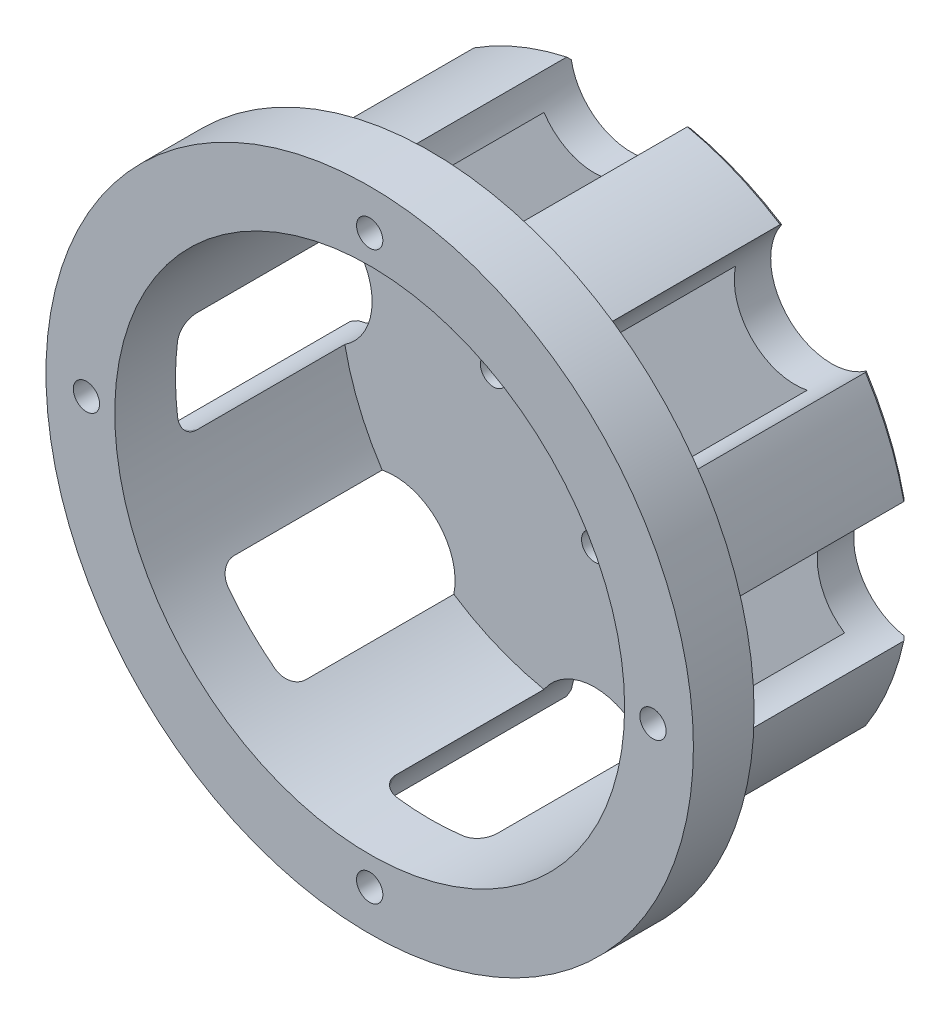
SolidWorks part; units mm, degrees
material "ABS PC"
ref_plane "Front Plane" through (0, 0, 0) normal (0, 0, 1) x (1, 0, 0)
ref_plane "Top Plane" through (0, 0, 0) normal (0, 1, 0) x (1, 0, 0)
ref_plane "Right Plane" through (0, 0, 0) normal (1, 0, 0) x (0, 0, -1)
sketch "Sketch1" plane through (0, 0, 0) normal (0, 0, 1) x (1, 0, 0)
  circle A0 centre (0, 0) radius 31.5
  circle A1 centre (0, 0) radius 35
  circle A2 centre (0, 0) radius 7
  circle A3 centre (0, 0) radius 12.5
  circle A4 centre (0, 12.5) radius 1.625
  circle A5 centre (12.5, 0) radius 1.625
  circle A6 centre (0, -12.5) radius 1.625
  circle A7 centre (-12.5, 0) radius 1.625
  point P17 (0, 0)
  dimension "D1" = 63
  dimension "D2" = 70
  dimension "D3" = 14
  dimension "D4" = 25
  dimension "D5" = 3.25
  dimension "D6" = 4
extrude "Boss-Extrude1" add sketch "Sketch1" along normal blind 4.5 contours A0 A7 A3 A4 A5 A6 | A7 A3 A6 A5 A4 A2 region at (-30.609, 0, 0) region at (10.5244, 0, 0)
extrude "Boss-Extrude2" add sketch "Sketch1<3>" along normal blind 32.3 contours A1 A0 region at (-34.0101, 0, 0)
sketch "Sketch1<3>" plane through (0, 0, 0) normal (0, 0, 1) x (1, 0, 0) same geometry as "Sketch1"
sketch "Sketch2" plane through (0, 0, 0) normal (0, 0, -1) x (-1, 0, 0)
  circle A0 centre (0, 35) radius 7.5
  circle A1 centre (0, 0) radius 35 construction
  circle A2 centre (24.7487, 24.7487) radius 7.5
  circle A3 centre (35, 0) radius 7.5
  circle A4 centre (24.7487, -24.7487) radius 7.5
  circle A5 centre (0, -35) radius 7.5
  circle A6 centre (-24.7487, -24.7487) radius 7.5
  circle A7 centre (-35, 0) radius 7.5
  circle A8 centre (-24.7487, 24.7487) radius 7.5
  point P20 (0, 0)
  dimension "D1" = 15
  dimension "D2" = 8
extrude "Cut-Extrude1" cut sketch "Sketch2" against normal blind 27.5
sketch "Sketch3" plane through (0, 0, 32.3) normal (0, 0, 1) x (1, 0, 0)
  circle A0 centre (0, 0) radius 40
  circle A1 centre (0, 0) radius 31.5
  dimension "D1" = 80
  dimension "D2" = 63
extrude "Boss-Extrude3" add sketch "Sketch3" against normal blind 7.5
sketch "Sketch4" plane through (0, 0, 32.3) normal (0, 0, 1) x (1, 0, 0)
  circle A0 centre (0, 35) radius 1.625
  circle A1 centre (35, 0) radius 1.625
  circle A2 centre (0, -35) radius 1.625
  circle A3 centre (-35, 0) radius 1.625
  point P13 (0, 0)
  dimension "D1" = 3.25
  dimension "D2" = 4
extrude "Cut-Extrude2" cut sketch "Sketch4" against normal blind 10
fillet "Fillet1" radius 2 24 edges at (-32.4625, -7.0577, 24.8) (27.945, 17.9639, 24.8) (-27.945, 17.9639, 24.8) (-7.0577, 32.4625, 24.8) (17.9639, 27.945, 24.8) (32.4625, -7.0577, 24.8) (32.4625, 7.0577, 24.8) (-17.9639, -27.945, 24.8) (7.0577, -32.4625, 24.8) (27.945, -17.9639, 24.8) (17.9639, -27.945, 24.8) (-7.0577, -32.4625, 24.8) (-27.945, -17.9639, 24.8) (-32.4625, 7.0577, 24.8) (-17.9639, 27.945, 24.8) (7.0577, 32.4625, 24.8) (13.3939, 32.3358, 24.8) (32.3358, 13.3939, 24.8) (32.3358, -13.3939, 24.8) (13.3939, -32.3358, 24.8) (-13.3939, -32.3358, 24.8) (-32.3358, -13.3939, 24.8) (-32.3358, 13.3939, 24.8) (-13.3939, 32.3358, 24.8)
chamfer "Chamfer1" distance 0.5 angle 45 8 edges at (-32.3358, -13.3939, 0) (-13.3939, -32.3358, 0) (13.3939, -32.3358, 0) (32.3358, -13.3939, 0) (32.3358, 13.3939, 0) (13.3939, 32.3358, 0) (-13.3939, 32.3358, 0) (-32.3358, 13.3939, 0)
